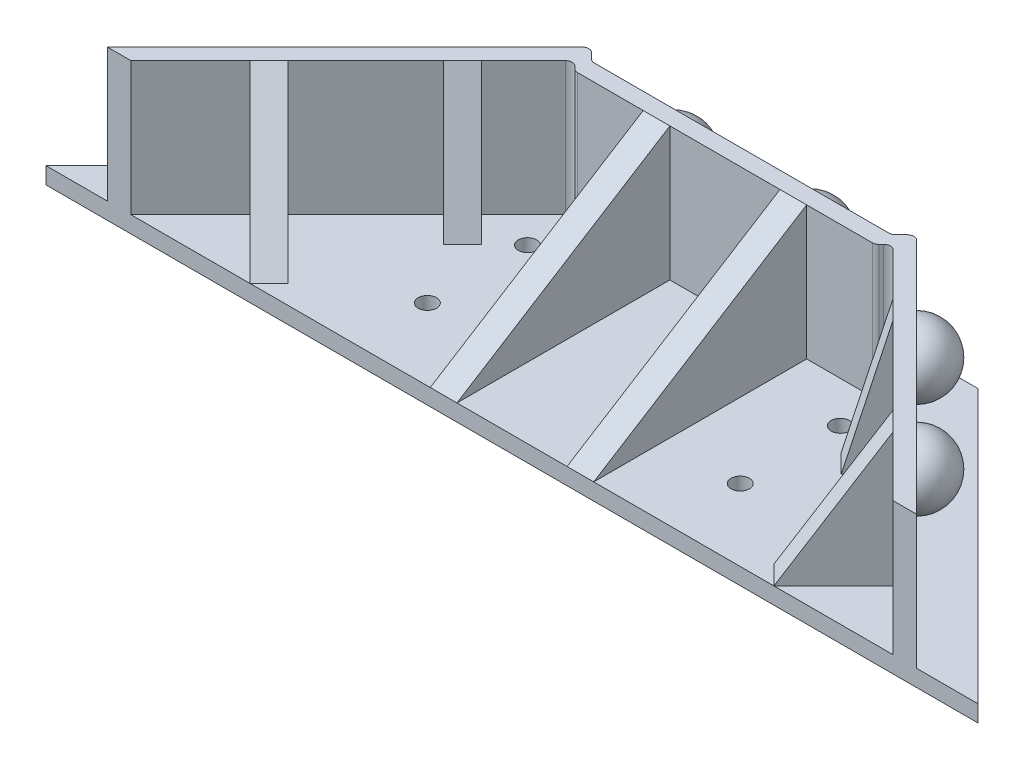
SolidWorks part; units mm, degrees
ref_plane "Front" through (0, 0, 0) normal (0, 0, 1) x (1, 0, 0)
ref_plane "Top" through (0, 0, 0) normal (0, 1, 0) x (1, 0, 0)
ref_plane "Right" through (0, 0, 0) normal (1, 0, 0) x (0, 0, -1)
sketch "Sketch2" plane through (0, 0, 0) normal (0, 1, 0) x (1, 0, 0)
  line L0 (0, 0) -> (40.9172, 40.9172)
  line L1 (0, 0) -> (139.7, 0)
  line L2 (139.7, 0) -> (98.7828, 40.9172)
  line L3 (98.7828, 40.9172) -> (40.9172, 40.9172)
  dimension "D1" = 139.7
  dimension "D2" = 57.8656
extrude "bracketBase" add sketch "Sketch2" along normal blind 2.5
sketch "Sketch3" plane through (0, 2.5, 0) normal (0, 1, 0) x (1, 0, 0)
  line L0 (69.85, 0) -> (69.85, 40.9172) construction
  line L1 (0, 0) -> (139.7, 0) construction
  line L2 (98.7828, 40.9172) -> (40.9172, 40.9172) construction
  circle A0 centre (8.0102, 3.7676) radius 1.375
  circle A1 centre (15.5454, 11.3027) radius 1.375
  circle A2 centre (46.4025, 25.7596) radius 1.375
  circle A3 centre (46.4025, 10.7596) radius 1.375
  circle A4 centre (93.2975, 10.7596) radius 1.375
  circle A5 centre (93.2975, 25.7596) radius 1.375
  circle A6 centre (124.1546, 11.3027) radius 1.375
  circle A7 centre (131.6898, 3.7676) radius 1.375
  dimension "D1" = 2.75
  dimension "D2" = 3.7676
  dimension "D3" = 8.0102
  dimension "D4" = 11.3027
  dimension "D5" = 15.5454
  dimension "D6" = 15
  dimension "D7" = 10.7596
  dimension "D8" = 5.4853
extrude "mountingHoles" cut sketch "Sketch3" against normal through all both and the other way through all
sketch "ballMountPressure" plane through (0, 2.5, 0) normal (0, 1, 0) x (1, 0, 0)
  line L0 (9.1093, 6.988) -> (40.9292, 38.8078) construction
  line L1 (40.9172, 40.9172) -> (0, 0) construction
  line L2 (9.1093, 6.988) -> (8.0487, 8.0487) construction
  line L3 (8.0487, 8.0487) -> (39.8685, 39.8685) construction
  line L4 (40.9292, 38.8078) -> (39.8685, 39.8685) construction
  line L5 (98.7828, 40.9172) -> (40.9172, 40.9172) construction
  line L6 (47.35, 40.9172) -> (92.35, 40.9172) construction
  line L7 (47.35, 40.9172) -> (47.35, 39.4172) construction
  line L8 (47.35, 39.4172) -> (92.35, 39.4172) construction
  line L9 (92.35, 40.9172) -> (92.35, 39.4172) construction
  line L10 (69.85, 0) -> (69.85, 14.6948) construction
  line L11 (0, 0) -> (139.7, 0) construction
  line L12 (130.5907, 6.988) -> (131.6513, 8.0487) construction
  line L13 (131.6513, 8.0487) -> (99.8315, 39.8685) construction
  line L14 (98.7708, 38.8078) -> (99.8315, 39.8685) construction
  line L15 (130.5907, 6.988) -> (98.7708, 38.8078) construction
  line L16 (12.6449, 3.4525) -> (44.4647, 35.2723)
  line L17 (12.6449, 3.4525) -> (14.4126, 1.6847)
  line L18 (14.4126, 1.6847) -> (46.2325, 33.5045)
  line L19 (46.2325, 33.5045) -> (44.4647, 35.2723)
  line L20 (125.2874, 1.6847) -> (93.4675, 33.5045)
  line L21 (47.35, 34.4172) -> (92.35, 34.4172)
  line L22 (47.35, 34.4172) -> (47.35, 31.9172)
  line L23 (47.35, 31.9172) -> (92.35, 31.9172)
  line L24 (92.35, 34.4172) -> (92.35, 31.9172)
  line L25 (127.0551, 3.4525) -> (125.2874, 1.6847)
  line L26 (127.0551, 3.4525) -> (95.2353, 35.2723)
  line L27 (93.4675, 33.5045) -> (95.2353, 35.2723)
  point P11 (69.85, 40.9172)
  point P14 (69.85, 40.9172)
  dimension "D1" = 1.5
  dimension "D2" = 45
  dimension "D3" = 8.0487
  dimension "D4" = 5
  dimension "D5" = 2.5
  dimension "D6" = 2.5
  dimension "D7" = 5
extrude "ballPressureWalls" add sketch "ballMountPressure" along normal blind 27.4754
sketch "Sketch4" plane through (0, 0, -34.4172) normal (0, 0, -1) x (-1, 0, 0)
  line L0 (-69.85, 29.9754) -> (-69.85, 2.5) construction
  line L1 (-92.35, 29.9754) -> (-47.35, 29.9754) construction
  line L2 (-92.35, 2.5) -> (-47.35, 2.5) construction
  line L3 (-80.1, 21.2377) -> (-80.1, 11.2377)
  arc A0 (-80.1, 21.2377) -> (-80.1, 11.2377) centre (-80.1, 16.2377) cw
  point P10 (-69.85, 16.2377)
  dimension "D1" = 5
  dimension "D2" = 10.25
revolve "ball1" add sketch "Sketch4" angle 180 about L3
sketch "Sketch5" plane through (0, 0, -34.4172) normal (0, 0, -1) x (-1, 0, 0)
  line L0 (-59.6, 21.2377) -> (-59.6, 11.2377)
  line L1 (-69.85, 29.9754) -> (-69.85, 2.5) construction
  line L2 (-92.35, 29.9754) -> (-47.35, 29.9754) construction
  line L3 (-98.7828, 2.5) -> (-40.9172, 2.5) construction
  arc A0 (-59.6, 21.2377) -> (-59.6, 11.2377) centre (-59.6, 16.2377) cw
  point P3 (-69.85, 16.2377)
  dimension "D1" = 10
  dimension "D2" = 10.25
revolve "ball2" add sketch "Sketch5" angle 180 about L0
sketch "Sketch6" plane through (65.2538, 0, -65.2538) normal (0.7071, 0, -0.7071) x (-0.7071, 0, -0.7071)
  line L0 (-75.1503, 21.2377) -> (-75.1503, 11.2377)
  line L1 (-64.9003, 29.9754) -> (-64.9003, 2.5) construction
  line L2 (-87.4003, 29.9754) -> (-42.4003, 29.9754) construction
  line L3 (-87.4003, 2.5) -> (-42.4003, 2.5) construction
  arc A0 (-75.1503, 21.2377) -> (-75.1503, 11.2377) centre (-75.1503, 16.2377) cw
  point P11 (-64.9003, 16.2377)
  dimension "D1" = 10
  dimension "D2" = 10.25
revolve "ball3" add sketch "Sketch6" angle 180 about L0
sketch "Sketch7" plane through (65.2538, 0, -65.2538) normal (0.7071, 0, -0.7071) x (-0.7071, 0, -0.7071)
  line L3 (-54.6503, 21.2377) -> (-54.6503, 11.2377)
  arc A0 (-54.6503, 21.2377) -> (-54.6503, 11.2377) centre (-54.6503, 16.2377) cw
  circle A1 centre (-75.1503, 16.2377) radius 5 construction
  circle A2 centre (-75.1503, 16.2377) radius 5 construction
  dimension "D1" = 10
  dimension "D2" = 20.5
revolve "Revolve4" add sketch "Sketch7" angle 180 about L3
sketch "Sketch8" plane through (4.5962, 0, 4.5962) normal (-0.7071, 0, -0.7071) x (-0.7071, 0, 0.7071)
  line L0 (-23.6326, 21.2377) -> (-23.6326, 11.2377)
  line L1 (-33.8826, 29.9754) -> (-33.8826, 2.5) construction
  line L2 (-56.3826, 29.9754) -> (-11.3826, 29.9754) construction
  line L3 (-56.3826, 2.5) -> (-11.3826, 2.5) construction
  arc A0 (-23.6326, 21.2377) -> (-23.6326, 11.2377) centre (-23.6326, 16.2377) cw
  point P9 (-33.8826, 16.2377)
  dimension "D1" = 10
  dimension "D2" = 10.25
revolve "Revolve5" add sketch "Sketch8" angle 180 about L0
sketch "Sketch9" plane through (4.5962, 0, 4.5962) normal (-0.7071, 0, -0.7071) x (-0.7071, 0, 0.7071)
  line L0 (-33.8826, 2.5) -> (-33.8826, 29.9754) construction
  line L1 (-56.3826, 2.5) -> (-11.3826, 2.5) construction
  line L2 (-56.3826, 29.9754) -> (-11.3826, 29.9754) construction
  line L3 (-44.1326, 21.2377) -> (-44.1326, 11.2377)
  arc A0 (-44.1326, 21.2377) -> (-44.1326, 11.2377) centre (-44.1326, 16.2377) cw
  point P9 (-33.8826, 16.2377)
  dimension "D1" = 10
  dimension "D2" = 10.25
revolve "Revolve6" add sketch "Sketch9" angle 180 about L3
sketch "Sketch10" plane through (0, 29.9754, 0) normal (0, 1, 0) x (1, 0, 0)
  line L0 (47.35, 31.9172) -> (45.9976, 33.2696)
  line L1 (14.4126, 1.6847) -> (46.2325, 33.5045) construction
  line L2 (47.35, 34.4172) -> (45.4798, 36.2874)
  line L3 (46.2325, 33.5045) -> (44.4647, 35.2723) construction
  line L4 (45.9976, 33.2696) -> (44.2298, 35.0374)
  line L5 (44.4647, 35.2723) -> (12.6449, 3.4525) construction
  line L6 (44.2298, 35.0374) -> (45.4798, 36.2874)
  line L7 (46.2325, 33.5045) -> (44.4647, 35.2723) construction
  line L8 (47.35, 34.4172) -> (47.35, 31.9172)
  line L9 (69.85, 31.9172) -> (69.85, 0) construction
  line L10 (47.35, 31.9172) -> (92.35, 31.9172) construction
  line L11 (0, 0) -> (139.7, 0) construction
  line L12 (14.4126, 1.6847) -> (12.7279, 0)
  line L13 (12.7279, 0) -> (9.1924, 0)
  line L14 (9.1924, 0) -> (12.6449, 3.4525)
  line L15 (44.4647, 35.2723) -> (12.6449, 3.4525) construction
  line L16 (14.4126, 1.6847) -> (46.2325, 33.5045) construction
  line L17 (12.6449, 3.4525) -> (14.4126, 1.6847)
  line L18 (92.35, 34.4172) -> (94.2202, 36.2874)
  line L19 (95.4702, 35.0374) -> (94.2202, 36.2874)
  line L20 (93.7024, 33.2696) -> (95.4702, 35.0374)
  line L21 (92.35, 31.9172) -> (93.7024, 33.2696)
  line L22 (92.35, 34.4172) -> (92.35, 31.9172)
  line L23 (130.5076, 0) -> (127.0551, 3.4525)
  line L24 (126.9721, 0) -> (130.5076, 0)
  line L25 (125.2874, 1.6847) -> (126.9721, 0)
  line L26 (127.0551, 3.4525) -> (125.2874, 1.6847)
extrude "Boss-Extrude2" add sketch "Sketch10" against normal up to surface (27.4754 mm away) up to face at (8.0102, 2.5, -2.3926)
fillet "Fillet1" radius 1 8 edges at (93.7024, 16.2377, -33.2696) (92.35, 16.2377, -31.9172) (45.9976, 16.2377, -33.2696) (47.35, 16.2377, -31.9172) (45.4798, 16.2377, -36.2874) (47.35, 16.2377, -34.4172) (92.35, 16.2377, -34.4172) (94.2202, 16.2377, -36.2874)
sketch "Sketch11" plane through (0, 29.9754, 0) normal (0, 1, 0) x (1, 0, 0)
  line L0 (69.85, 31.9172) -> (69.85, 0) construction
  line L1 (47.7642, 31.9172) -> (91.9358, 31.9172) construction
  line L2 (12.7279, 0) -> (126.9721, 0) construction
  line L3 (46.4025, 25.7596) -> (69.85, 25.7596) construction
  line L4 (46.4025, 10.7596) -> (69.85, 10.7596) construction
  line L5 (47.7642, 31.9172) -> (91.9358, 31.9172) construction
  line L6 (55.6262, 31.9172) -> (60.6262, 31.9172)
  line L7 (55.6262, 31.9172) -> (55.6262, 0)
  line L8 (55.6262, 0) -> (60.6262, 0)
  line L9 (60.6262, 31.9172) -> (60.6262, 0)
  line L10 (84.0738, 0) -> (79.0738, 0)
  line L11 (79.0738, 31.9172) -> (79.0738, 0)
  line L12 (84.0738, 31.9172) -> (79.0738, 31.9172)
  line L13 (84.0738, 31.9172) -> (84.0738, 0)
  line L14 (17.7714, 8.579) -> (24.8425, 15.6501) construction
  line L15 (44.7727, 35.5803) -> (9.1924, 0) construction
  line L16 (39.3382, 30.1458) -> (32.2671, 23.0747) construction
  line L17 (44.7727, 35.5803) -> (9.1924, 0) construction
  line L18 (35.8026, 23.0747) -> (44.3816, 14.4957)
  line L19 (12.7279, 0) -> (45.2904, 32.5625) construction
  line L20 (44.3816, 14.4957) -> (47.9172, 18.0312)
  line L21 (47.9172, 18.0312) -> (39.3382, 26.6102)
  line L22 (12.7279, 0) -> (45.2904, 32.5625) construction
  line L23 (39.3382, 26.6102) -> (35.8026, 23.0747)
  line L24 (35.8026, 26.6102) -> (37.5704, 24.8425) construction
  line L25 (21.3069, 12.1146) -> (23.0747, 10.3468) construction
  line L26 (21.3069, 8.579) -> (24.8425, 12.1146)
  line L27 (21.3069, 8.579) -> (29.886, 0)
  line L28 (29.886, 0) -> (33.4215, 3.5355)
  line L29 (33.4215, 3.5355) -> (24.8425, 12.1146)
  line L30 (109.814, 0) -> (106.2785, 3.5355)
  line L31 (118.3931, 8.579) -> (109.814, 0)
  line L32 (118.3931, 8.579) -> (114.8575, 12.1146)
  line L33 (106.2785, 3.5355) -> (114.8575, 12.1146)
  line L34 (91.7828, 18.0312) -> (100.3618, 26.6102)
  line L35 (95.3184, 14.4957) -> (91.7828, 18.0312)
  line L36 (103.8974, 23.0747) -> (95.3184, 14.4957)
  line L37 (100.3618, 26.6102) -> (103.8974, 23.0747)
  arc A0 (24.8425, 15.6501) -> (17.7714, 8.579) centre (21.3069, 12.1146) ccw construction
  arc A1 (39.3382, 30.1458) -> (32.2671, 23.0747) centre (35.8026, 26.6102) ccw construction
  point P18 (58.1262, 31.9172)
  point P19 (58.1262, 25.7596)
  point P50 (37.5704, 24.8425)
  point P55 (23.0747, 10.3468)
  dimension "D1" = 5
  dimension "D2" = 5
extrude "Boss-Extrude3" add sketch "Sketch11" against normal up to surface (27.4754 mm away) up to face at (69.85, 2.5, -25.895)
sketch "Sketch12" plane through (32.9742, 0, -32.9742) normal (0.7071, 0, -0.7071) x (-0.7071, 0, -0.7071)
  line L0 (-9, 29.9754) -> (-21.1326, 2.5)
  line L1 (-21.1326, 2.5) -> (-21.1326, 29.9754)
  line L2 (-21.1326, 29.9754) -> (-9, 29.9754)
extrude "Cut-Extrude1" cut sketch "Sketch12" against normal through all
sketch "Sketch13" plane through (55.6262, 0, 0) normal (-1, 0, 0) x (0, 0, 1)
  line L0 (-31.9172, 29.9754) -> (0, 2.5)
  line L1 (0, 2.5) -> (0, 29.9754)
  line L2 (0, 29.9754) -> (-31.9172, 29.9754)
extrude "Cut-Extrude2" cut sketch "Sketch13" against normal up to surface (28.4475 mm away) up to face at (84.0738, 16.2377, -15.9586)
sketch "Sketch14" plane through (54.907, 0, 54.907) normal (0.7071, 0, 0.7071) x (0.7071, 0, -0.7071)
  line L0 (77.6503, 2.5) -> (89.7828, 29.9754)
  line L1 (89.7828, 29.9754) -> (77.6503, 29.9754)
  line L2 (77.6503, 29.9754) -> (77.6503, 2.5)
extrude "Cut-Extrude3" cut sketch "Sketch14" against normal up to surface (25.5 mm away) up to face at (96.0723, 16.2377, -22.3207)
sketch "Sketch15" plane through (0, 0, -31.9172) normal (0, 0, 1) x (1, 0, 0)
  line L0 (60.6262, 29.9754) -> (79.0738, 29.9754) construction
  line L1 (44.7727, 29.9754) -> (94.9273, 29.9754)
  line L2 (44.7727, 29.9754) -> (44.7727, 22.5)
  line L3 (44.7727, 22.5) -> (94.9273, 22.5)
  line L4 (94.9273, 29.9754) -> (94.9273, 22.5)
  line L5 (44.7727, 29.9754) -> (44.7727, 2.5) construction
  point P6 (69.85, 29.9754)
  point P7 (69.85, 29.9754)
  dimension "D2" = 7.4754
extrude "Cut-Extrude4" cut sketch "Sketch15" against normal through all
sketch "Sketch16" plane through (63.486, 0, -63.486) normal (-0.7071, 0, 0.7071) x (0.7071, 0, 0.7071)
  line L0 (57.1503, 29.9754) -> (72.6503, 29.9754) construction
  line L1 (92.2828, 2.5) -> (92.2828, 29.9754) construction
  line L2 (37.5177, 22.5) -> (92.2828, 22.5)
  line L3 (37.5177, 22.5) -> (37.5177, 29.9754)
  line L4 (37.5177, 29.9754) -> (92.2828, 29.9754)
  line L5 (92.2828, 22.5) -> (92.2828, 29.9754)
  point P0 (64.9003, 29.9754)
  point P7 (64.9003, 29.9754)
  dimension "D2" = 7.4754
extrude "Cut-Extrude5" cut sketch "Sketch16" against normal through all
sketch "Sketch17" plane through (6.364, 0, 6.364) normal (0.7071, 0, 0.7071) x (0.7071, 0, -0.7071)
  line L0 (26.1326, 29.9754) -> (41.6326, 29.9754) construction
  line L2 (6.5, 22.5) -> (61.2651, 22.5)
  line L3 (6.5, 22.5) -> (6.5, 29.9754)
  line L4 (6.5, 29.9754) -> (61.2651, 29.9754)
  line L5 (61.2651, 22.5) -> (61.2651, 29.9754)
  line L6 (6.5, 2.5) -> (6.5, 29.9754) construction
  point P0 (33.8826, 29.9754)
  point P7 (33.8826, 29.9754)
  dimension "D1" = 7.4754
extrude "Cut-Extrude6" cut sketch "Sketch17" against normal through all
sketch "Sketch19" plane through (14.943, 0, -14.943) normal (-0.7071, 0, 0.7071) x (0.7071, 0, 0.7071)
  line L4 (21.1326, 2.5) -> (9, 29.9754)
  line L5 (9, 29.9754) -> (9, 22.5)
  line L6 (9, 22.5) -> (9, 2.5)
  line L7 (9, 2.5) -> (21.1326, 2.5)
  line L8 (21.1326, 2.5) -> (9, 29.9754)
  line L9 (9, 29.9754) -> (9, 22.5)
  line L10 (9, 22.5) -> (9, 2.5)
  line L11 (9, 2.5) -> (21.1326, 2.5)
  dimension "D1" = 0
extrude "Cut-Extrude7" cut sketch "Sketch19" against normal up to surface (25.5 mm away) up to face at (41.4829, 14.3688, -24.4655)
sketch "Sketch20" plane through (55.6262, 0, 0) normal (-1, 0, 0) x (0, 0, 1)
  line L4 (0, 2.5) -> (-31.9172, 29.9754)
  line L5 (-31.9172, 29.9754) -> (-31.9172, 22.5)
  line L6 (-31.9172, 22.5) -> (-31.9172, 2.5)
  line L7 (-31.9172, 2.5) -> (0, 2.5)
  line L8 (0, 2.5) -> (-31.9172, 29.9754)
  line L9 (-31.9172, 29.9754) -> (-31.9172, 22.5)
  line L10 (-31.9172, 22.5) -> (-31.9172, 2.5)
  line L11 (-31.9172, 2.5) -> (0, 2.5)
  dimension "D1" = 0
extrude "Cut-Extrude8" cut sketch "Sketch20" against normal up to surface (28.4475 mm away) up to face at (84.0738, 14.3688, -23.9379)
sketch "Sketch21" plane through (54.907, 0, 54.907) normal (0.7071, 0, 0.7071) x (0.7071, 0, -0.7071)
  line L4 (89.7828, 29.9754) -> (77.6503, 2.5)
  line L5 (77.6503, 2.5) -> (89.7828, 2.5)
  line L6 (89.7828, 2.5) -> (89.7828, 22.5)
  line L7 (89.7828, 22.5) -> (89.7828, 29.9754)
  line L8 (89.7828, 29.9754) -> (77.6503, 2.5)
  line L9 (77.6503, 2.5) -> (89.7828, 2.5)
  line L10 (89.7828, 2.5) -> (89.7828, 22.5)
  line L11 (89.7828, 22.5) -> (89.7828, 29.9754)
  dimension "D1" = 0
extrude "Cut-Extrude9" cut sketch "Sketch21" against normal up to surface (25.5 mm away) up to face at (98.2171, 14.3688, -24.4655)
sketch "Sketch22" plane through (0, 22.5, 0) normal (0, 1, 0) x (1, 0, 0)
  line L0 (57.6, 34.4172) -> (61.6, 34.4172)
  line L1 (47.7642, 34.4172) -> (91.9358, 34.4172) construction
  line L2 (69.85, 31.9172) -> (69.85, 0) construction
  line L3 (47.7642, 31.9172) -> (91.9358, 31.9172) construction
  line L4 (12.7279, 0) -> (126.9721, 0) construction
  line L5 (107.4329, 23.0747) -> (114.8575, 15.6501) construction
  line L8 (19.8927, 10.7003) -> (30.5931, 0)
  line L9 (24.8425, 15.6501) -> (32.2671, 23.0747) construction
  line L10 (22.7212, 13.5288) -> (33.4215, 2.8284)
  line L11 (57.6, 34.4172) -> (57.6, 0)
  line L12 (57.6, 0) -> (61.6, 0)
  line L13 (61.6, 0) -> (61.6, 34.4172)
  line L14 (82.1, 0) -> (78.1, 0)
  line L15 (82.1, 34.4172) -> (82.1, 0)
  line L16 (82.1, 34.4172) -> (78.1, 34.4172)
  line L17 (78.1, 0) -> (78.1, 34.4172)
  line L18 (34.3884, 25.196) -> (37.2168, 28.0245)
  line L19 (9.1924, 0) -> (44.7727, 35.5803) construction
  line L20 (19.8927, 10.7003) -> (22.7212, 13.5288)
  line L21 (30.5931, 0) -> (33.4215, 2.8284)
  line L22 (34.3884, 25.196) -> (40.0453, 19.5392)
  line L23 (37.2168, 28.0245) -> (42.8737, 22.3676)
  line L24 (40.0453, 19.5392) -> (42.8737, 22.3676)
  line L25 (105.3116, 25.196) -> (102.4832, 28.0245)
  line L26 (105.3116, 25.196) -> (99.6547, 19.5392)
  line L27 (99.6547, 19.5392) -> (96.8263, 22.3676)
  line L28 (102.4832, 28.0245) -> (96.8263, 22.3676)
  line L29 (119.8073, 10.7003) -> (116.9788, 13.5288)
  line L30 (119.8073, 10.7003) -> (109.1069, 0)
  line L31 (109.1069, 0) -> (106.2785, 2.8284)
  line L32 (116.9788, 13.5288) -> (106.2785, 2.8284)
  arc A0 (64.6, 34.4172) -> (54.6, 34.4172) centre (59.6, 34.4172) ccw construction
  arc A1 (64.6, 34.4172) -> (54.6, 34.4172) centre (59.6, 34.4172) ccw construction
  arc A2 (85.1, 34.4172) -> (75.1, 34.4172) centre (80.1, 34.4172) ccw construction
  arc A3 (85.1, 34.4172) -> (75.1, 34.4172) centre (80.1, 34.4172) ccw construction
  arc A4 (107.4329, 23.0747) -> (100.3618, 30.1458) centre (103.8974, 26.6102) ccw construction
  arc A5 (107.4329, 23.0747) -> (100.3618, 30.1458) centre (103.8974, 26.6102) ccw construction
  arc A6 (121.9286, 8.579) -> (114.8575, 15.6501) centre (118.3931, 12.1146) ccw construction
  arc A7 (121.9286, 8.579) -> (114.8575, 15.6501) centre (118.3931, 12.1146) ccw construction
  arc A8 (24.8425, 15.6501) -> (17.7714, 8.579) centre (21.3069, 12.1146) ccw construction
  arc A9 (24.8425, 15.6501) -> (17.7714, 8.579) centre (21.3069, 12.1146) ccw construction
  arc A10 (39.3382, 30.1458) -> (32.2671, 23.0747) centre (35.8026, 26.6102) ccw construction
  arc A11 (39.3382, 30.1458) -> (32.2671, 23.0747) centre (35.8026, 26.6102) ccw construction
  point P23 (59.6, 34.4172)
  point P26 (80.1, 34.4172)
  point P45 (35.8026, 26.6102)
  point P48 (21.3069, 12.1146)
  dimension "D1" = 4
  dimension "D2" = 8
extrude "Boss-Extrude4" add sketch "Sketch22" against normal up to surface (20 mm away) up to face at (69.85, 2.5, -25.9182)
sketch "Sketch23" plane through (57.6, 0, 0) normal (-1, 0, 0) x (0, 0, 1)
  line L0 (-31.9172, 22.5) -> (0, 2.5)
  line L1 (0, 2.5) -> (0, 22.5)
  line L2 (0, 22.5) -> (-31.9172, 22.5)
extrude "Cut-Extrude10" cut sketch "Sketch23" against normal up to surface (24.5 mm away) up to face at (82.1, 12.5, -15.9586)
sketch "Sketch24" plane through (15.2965, 0, -15.2965) normal (-0.7071, 0, 0.7071) x (0.7071, 0, 0.7071)
  line L0 (9, 22.5) -> (21.6326, 2.5)
  line L1 (21.6326, 2.5) -> (21.6326, 22.5)
  line L2 (21.6326, 22.5) -> (9, 22.5)
extrude "Cut-Extrude11" cut sketch "Sketch24" against normal up to surface (4 mm away) up to face at (28.9552, 12.5, -7.2947)
sketch "Sketch25" plane through (54.5535, 0, 54.5535) normal (0.7071, 0, 0.7071) x (0.7071, 0, -0.7071)
  line L0 (89.7828, 22.5) -> (77.1503, 2.5)
  line L1 (77.1503, 2.5) -> (77.1503, 22.5)
  line L2 (77.1503, 22.5) -> (89.7828, 22.5)
extrude "Cut-Extrude12" cut sketch "Sketch25" against normal up to surface (4 mm away) up to face at (110.7448, 12.5, -7.2947)
sketch "Sketch26" plane through (29.7922, 0, -29.7922) normal (-0.7071, 0, 0.7071) x (0.7071, 0, 0.7071)
  line L0 (9, 22.5) -> (14.5, 22.5) construction
  line L1 (9, 22.5) -> (14.5, 22.5)
  line L2 (14.5, 2.5) -> (14.5, 22.5) construction
  line L3 (14.5, 2.5) -> (14.5, 22.5)
  line L4 (9, 22.5) -> (14.5, 2.5)
extrude "Cut-Extrude13" cut sketch "Sketch26" against normal up to surface (4 mm away) up to face at (40.9292, 12.5, -24.3121)
sketch "Sketch27" plane through (40.0578, 0, 40.0578) normal (0.7071, 0, 0.7071) x (0.7071, 0, -0.7071)
  line L0 (84.2828, 22.5) -> (89.7828, 22.5) construction
  line L1 (84.2828, 22.5) -> (89.7828, 22.5)
  line L2 (84.2828, 2.5) -> (84.2828, 22.5) construction
  line L3 (84.2828, 2.5) -> (84.2828, 22.5)
  line L4 (89.7828, 22.5) -> (84.2828, 2.5)
extrude "Cut-Extrude14" cut sketch "Sketch27" against normal up to surface (4 mm away) up to face at (98.7708, 12.5, -24.3121)
sketch "Sketch28" plane through (0, 2.5, 0) normal (0, 1, 0) x (1, 0, 0)
  line L10 (46.1869, 35.5803) -> (47.0571, 34.7101)
  line L11 (47.7642, 34.4172) -> (91.9358, 34.4172)
  line L12 (92.6429, 34.7101) -> (93.5131, 35.5803)
  line L13 (94.9273, 35.5803) -> (130.5076, 0)
  line L14 (130.5076, 0) -> (139.7, 0)
  line L15 (139.7, 0) -> (98.7828, 40.9172)
  line L16 (98.7828, 40.9172) -> (40.9172, 40.9172)
  line L17 (40.9172, 40.9172) -> (0, 0)
  line L18 (0, 0) -> (9.1924, 0)
  line L19 (9.1924, 0) -> (44.7727, 35.5803)
  line L20 (46.1869, 35.5803) -> (47.0571, 34.7101)
  line L21 (47.7642, 34.4172) -> (91.9358, 34.4172)
  line L22 (92.6429, 34.7101) -> (93.5131, 35.5803)
  line L23 (94.9273, 35.5803) -> (130.5076, 0)
  line L24 (130.5076, 0) -> (139.7, 0)
  line L25 (139.7, 0) -> (98.7828, 40.9172)
  line L26 (98.7828, 40.9172) -> (40.9172, 40.9172)
  line L27 (40.9172, 40.9172) -> (0, 0)
  line L28 (0, 0) -> (9.1924, 0)
  line L29 (9.1924, 0) -> (44.7727, 35.5803)
  arc A4 (47.0571, 34.7101) -> (47.7642, 34.4172) centre (47.7642, 35.4172) ccw
  arc A5 (91.9358, 34.4172) -> (92.6429, 34.7101) centre (91.9358, 35.4172) ccw
  arc A6 (94.9273, 35.5803) -> (93.5131, 35.5803) centre (94.2202, 34.8732) ccw
  arc A7 (46.1869, 35.5803) -> (44.7727, 35.5803) centre (45.4798, 34.8732) ccw
  arc A8 (47.0571, 34.7101) -> (47.7642, 34.4172) centre (47.7642, 35.4172) ccw
  arc A9 (91.9358, 34.4172) -> (92.6429, 34.7101) centre (91.9358, 35.4172) ccw
  arc A10 (94.9273, 35.5803) -> (93.5131, 35.5803) centre (94.2202, 34.8732) ccw
  arc A11 (46.1869, 35.5803) -> (44.7727, 35.5803) centre (45.4798, 34.8732) ccw
  dimension "D1" = 0
extrude "Boss-Extrude5" add sketch "Sketch28" against normal up to surface (2.5 mm away) up to face at (8.0102, 0, -2.3926)
